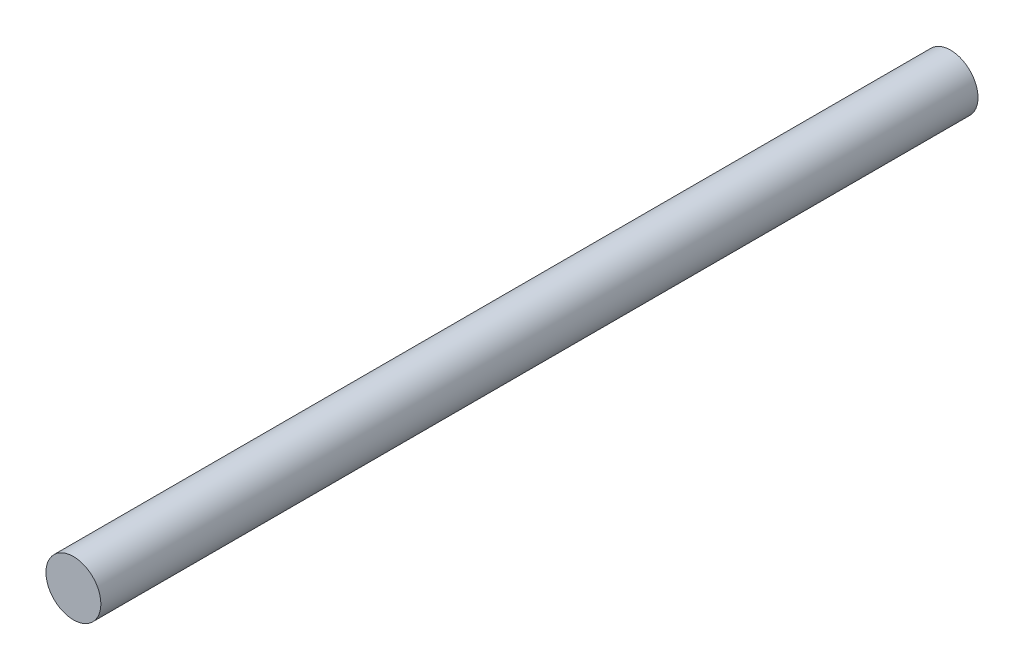
SolidWorks part; units mm, degrees
material "AISI 304"
ref_plane "前视基准面" through (0, 0, 0) normal (0, 0, 1) x (1, 0, 0)
ref_plane "上视基准面" through (0, 0, 0) normal (0, 1, 0) x (1, 0, 0)
ref_plane "右视基准面" through (0, 0, 0) normal (1, 0, 0) x (0, 0, -1)
other "Configuration Table"
sketch "草图1" plane through (0, 0, 0) normal (0, 0, 1) x (1, 0, 0)
  line L0 (0, 0) -> (-6.2607, 0) construction
  line L1 (0, 0) -> (6.2607, 0) construction
  circle A0 centre (0, 0) radius 6.2607
  dimension "D1" = 12.5213
extrude "凸台-拉伸1" add sketch "草图1" along normal blind 200
